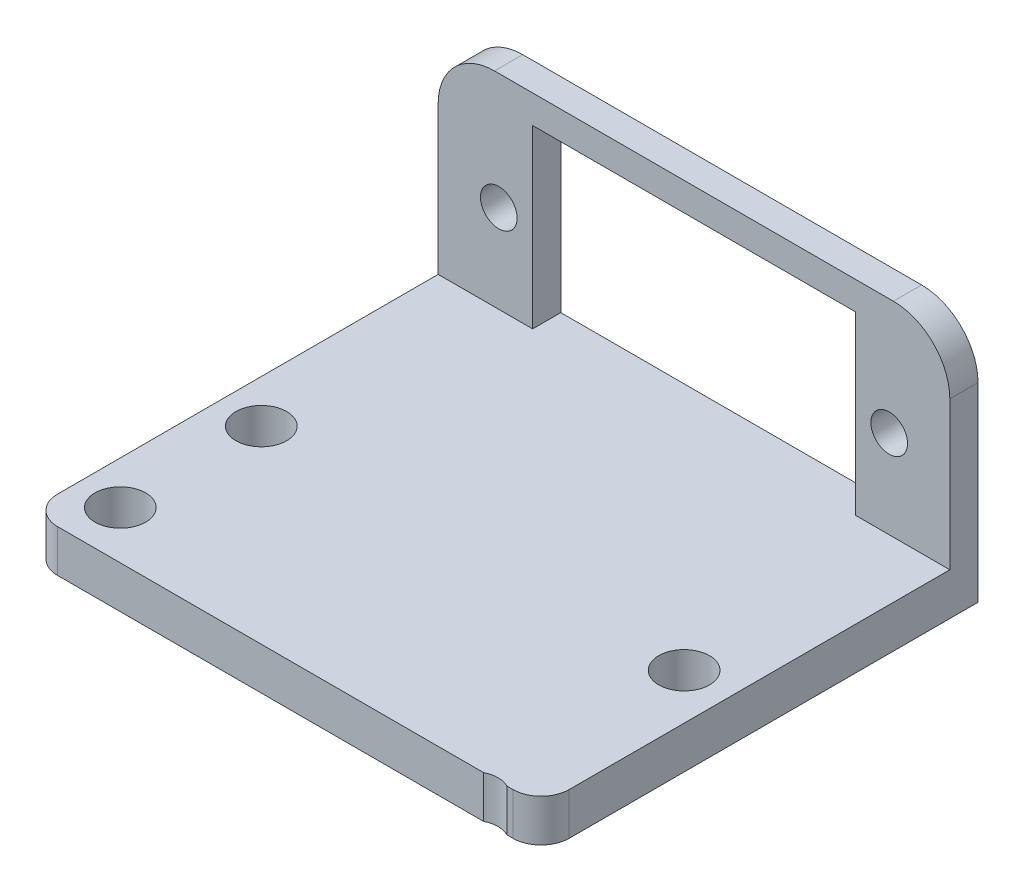
SolidWorks part; units mm, degrees
ref_plane "Front Plane" through (0, 0, 0) normal (0, 0, 1) x (1, 0, 0)
ref_plane "Top Plane" through (0, 0, 0) normal (0, 1, 0) x (1, 0, 0)
ref_plane "Right Plane" through (0, 0, 0) normal (1, 0, 0) x (0, 0, -1)
sketch "Sketch1" plane through (0, 0, 0) normal (0, 0, 1) x (1, 0, 0)
  line L1 (1.5, 2.7805) -> (1.5, 14.8805) construction
  line L2 (-0.5, 8.8305) -> (35.8, 8.8305) construction
  line L3 (-0.5, 17.0805) -> (35.8, 17.0805)
  line L4 (-0.5, 17.0805) -> (-0.5, 0.5805)
  line L5 (-0.5, 0.5805) -> (35.8, 0.5805)
  line L6 (35.8, 17.0805) -> (35.8, 0.5805)
  line L7 (1.5, 14.8805) -> (33.8, 14.8805) construction
  line L8 (17.65, 14.8805) -> (17.65, 8.8305) construction
  line L9 (6.4, 14.8805) -> (6.4, 2.7805) construction
  line L11 (6.2, 15.0805) -> (29.1, 15.0805)
  line L12 (6.2, 15.0805) -> (6.2, 2.5805)
  line L13 (6.2, 2.5805) -> (29.1, 2.5805)
  line L14 (29.1, 15.0805) -> (29.1, 2.5805)
  point P10 (1.5, 8.8305)
  point P21 (17.65, 15.0805)
  point P22 (6.2, 8.8305)
  dimension "D1" = 2
  dimension "D2" = 2.2
  dimension "D3" = 0.2
  dimension "D4" = 0.2
extrude "Boss-Extrude1" add sketch "Sketch1" along normal blind 2
fillet "Fillet1" radius 4 2 edges at (35.8, 17.0805, 1) (-0.5, 17.0805, 1)
sketch "Sketch2" plane through (0, 0, 2) normal (0, 0, 1) x (1, 0, 0)
  point P0 (31.5, 8.8305)
  point P3 (3.8, 8.8305)
hole_wizard "M2 Clearance Hole1" positions "Sketch2" profile "Sketch3" hole size "M2" standard "ANSI Metric" end condition through all
sketch "Sketch3" plane through (31.5, 8.8305, 2) normal (1, 0, 0) x (0, -1, 0)
  line L0 (0, 0) -> (0, 2)
  line L1 (0, 2) -> (1.3, 2)
  line L2 (1.3, 2) -> (1.3, 0)
  line L5 (1.3, 0) -> (0, 0)
  line L11 (0, -6.35) -> (0, 107.95) construction
  dimension "Thru Hole Dia." = 2.6
  dimension "Thru Hole Depth" = 2
sketch "Sketch4" plane through (0, 0, 2) normal (0, 0, 1) x (1, 0, 0)
  line L0 (-0.5, 13.0805) -> (-0.5, 0.5805) construction
  line L1 (-0.5, 2.5805) -> (35.8, 2.5805)
  line L2 (-0.5, 2.5805) -> (-0.5, -0.4195)
  line L3 (-0.5, -0.4195) -> (35.8, -0.4195)
  line L4 (35.8, 2.5805) -> (35.8, -0.4195)
  line L5 (6.2, 2.5805) -> (29.1, 2.5805) construction
  line L6 (35.8, 0.5805) -> (35.8, 13.0805) construction
  dimension "D1" = 3
extrude "Boss-Extrude2" add sketch "Sketch4" along normal blind 29
extrude "Boss-Extrude3" add sketch "Sketch4<2>" against normal up to surface (2 mm away) up to face at (32.8, 8.8305, 0)
sketch "Sketch4<2>" plane through (0, 0, 2) normal (0, 0, 1) x (1, 0, 0) same geometry as "Sketch4"
fillet "Fillet2" radius 2 2 edges at (35.8, 1.0805, 31) (-0.5, 1.0805, 31)
sketch "Sketch5" plane through (0, 2.5805, 0) normal (0, 1, 0) x (1, 0, 0)
  point P0 (2.55, -17.6)
  point P3 (2.55, -27.6)
  point P6 (32.55, -17.6)
  point P9 (32.55, -32.6)
hole_wizard "M3 Clearance Hole1" positions "Sketch5" profile "Sketch6" hole size "M3" standard "ANSI Metric" end condition through all
sketch "Sketch6" plane through (2.55, 2.5805, 17.6) normal (1, 0, 0) x (0, 0, 1)
  line L0 (0, 0) -> (0, 3)
  line L1 (0, 3) -> (1.8, 3)
  line L2 (1.8, 3) -> (1.8, 0)
  line L5 (1.8, 0) -> (0, 0)
  line L11 (0, -6.35) -> (0, 107.95) construction
  dimension "Thru Hole Dia." = 3.6
  dimension "Thru Hole Depth" = 3
